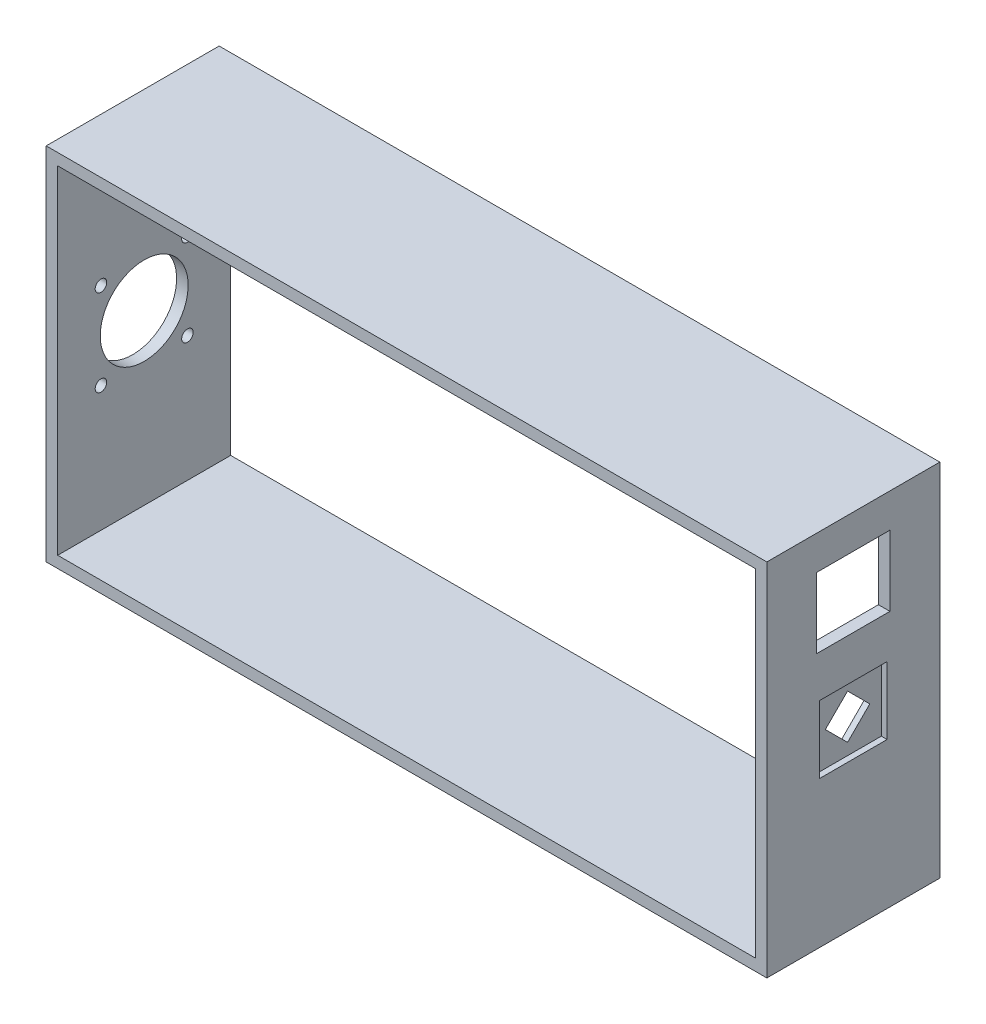
SolidWorks part; units mm, degrees
ref_plane "Ebene vorne" through (0, 0, 0) normal (0, 0, 1) x (1, 0, 0)
ref_plane "Ebene oben" through (0, 0, 0) normal (0, 1, 0) x (1, 0, 0)
ref_plane "Ebene rechts" through (0, 0, 0) normal (1, 0, 0) x (0, 0, -1)
sketch "Skizze1" plane through (0, 0, 0) normal (0, 0, 1) x (1, 0, 0)
  line L1 (0, 125) -> (250, 125)
  line L2 (0, 125) -> (0, 0)
  line L3 (0, 0) -> (250, 0)
  line L4 (250, 125) -> (250, 0)
  line L5 (246, 121) -> (4, 121)
  line L6 (246, 121) -> (246, 4)
  line L7 (246, 4) -> (4, 4)
  line L8 (4, 121) -> (4, 4)
  dimension "D1" = 250
  dimension "D2" = 125
  dimension "D3" = 4
  dimension "D4" = 4
  dimension "D5" = 4
  dimension "D6" = 4
extrude "Aufsatz-Linear austragen1" add sketch "Skizze1" along normal blind 60
sketch "Skizze2" plane through (0, 0, 0) normal (-1, 0, 0) x (0, 0, 1)
  line L0 (0, 62.5) -> (60, 62.5) construction
  line L1 (30, 125) -> (30, 0) construction
  line L2 (60, 125) -> (0, 125) construction
  line L3 (60, 0) -> (0, 0) construction
  line L4 (0, 125) -> (0, 0) construction
  line L5 (60, 125) -> (60, 0) construction
  line L6 (15, 77.5) -> (45, 77.5) construction
  line L7 (45, 77.5) -> (45, 47.5) construction
  line L8 (45, 47.5) -> (15, 47.5) construction
  line L9 (15, 47.5) -> (15, 77.5) construction
  circle A0 centre (30, 62.5) radius 15.25
  circle A1 centre (15, 77.5) radius 2
  circle A2 centre (45, 77.5) radius 2
  circle A3 centre (45, 47.5) radius 2
  circle A4 centre (15, 47.5) radius 2
  point P17 (30, 62.5)
  point P21 (30, 77.5)
  point P22 (53.5816, 62.5)
  point P24 (15, 62.5)
  dimension "D1" = 30
  dimension "D2" = 30
extrude "Schnitt-Linear austragen1" cut sketch "Skizze2" against normal blind 10
sketch "Skizze8" plane through (250, 0, 0) normal (1, 0, 0) x (0, 0, -1)
  line L0 (-60, 62.5) -> (0, 62.5) construction
  line L1 (-60, 0) -> (-60, 125) construction
  line L2 (0, 0) -> (0, 125) construction
  line L3 (-30, 125) -> (-30, 0) construction
  line L4 (-60, 125) -> (0, 125) construction
  line L5 (-60, 0) -> (0, 0) construction
  line L6 (-30, 70.2075) -> (-37.7075, 62.5)
  line L11 (-30, 70.2075) -> (-22.2925, 62.5)
  line L12 (-37.7075, 62.5) -> (-30, 54.7925)
  line L13 (-22.2925, 62.5) -> (-30, 54.7925)
  line L14 (-30, 70.2075) -> (-30, 54.7925) construction
  line L15 (-37.7075, 62.5) -> (-22.2925, 62.5) construction
  line L21 (-42.7, 113.2) -> (-17.3, 113.2)
  line L22 (-42.7, 113.2) -> (-42.7, 88.8)
  line L23 (-42.7, 88.8) -> (-17.3, 88.8)
  line L24 (-17.3, 113.2) -> (-17.3, 88.8)
  line L25 (-42.7, 113.2) -> (-17.3, 88.8) construction
  line L26 (-42.7, 88.8) -> (-17.3, 113.2) construction
  point P12 (-30, 101)
  point P13 (-30, 62.5)
  dimension "D3" = 25.4
  dimension "D4" = 24.4
  dimension "D1" = 10.9
  dimension "D2" = 10.9
  dimension "D5" = 24
extrude "Schnitt-Linear austragen6" cut sketch "Skizze8" against normal blind 22
sketch "Skizze9" plane through (250, 0, 0) normal (1, 0, 0) x (0, 0, -1)
sketch "Skizze10" plane through (250, 0, 0) normal (1, 0, 0) x (0, 0, -1)
  line L1 (-41.7075, 74.2075) -> (-18.2925, 74.2075)
  line L2 (-41.7075, 74.2075) -> (-41.7075, 50.7925)
  line L3 (-41.7075, 50.7925) -> (-18.2925, 50.7925)
  line L4 (-18.2925, 74.2075) -> (-18.2925, 50.7925)
  dimension "D1" = 4
  dimension "D2" = 4
  dimension "D3" = 4
  dimension "D4" = 4
extrude "Schnitt-Linear austragen7" cut sketch "Skizze10" against normal blind 2
